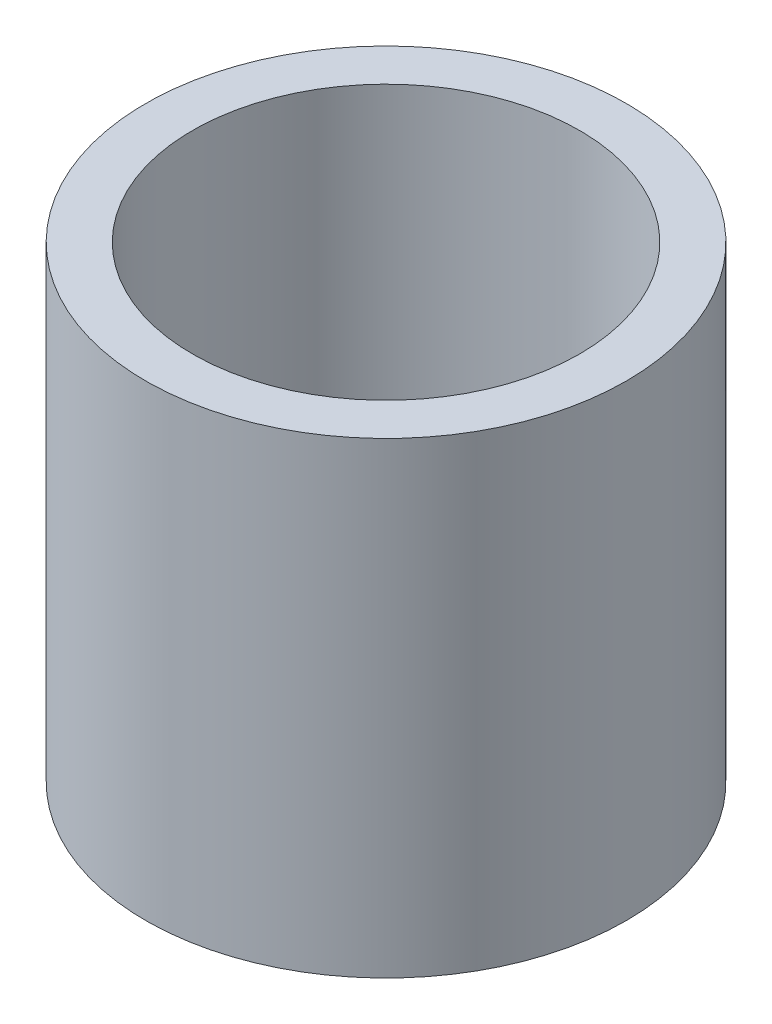
SolidWorks part; units mm, degrees
material "AISI 321 Annealed Stainless Steel (SS)"
ref_plane "Front Plane" through (0, 0, 0) normal (0, 0, 1) x (1, 0, 0)
ref_plane "Top Plane" through (0, 0, 0) normal (0, 1, 0) x (1, 0, 0)
ref_plane "Right Plane" through (0, 0, 0) normal (1, 0, 0) x (0, 0, -1)
sketch "Sketch1" plane through (0, 0, 0) normal (0, 0, 1) x (1, 0, 0)
  line L0 (0, -1459.8926) -> (0, 71534.7381) construction
  line L1 (16, -17.5) -> (16, -4.5)
  line L2 (16, -4.5) -> (14.5, -4.5)
  line L5 (14.5, -4.5) -> (14.5, 17.5)
  line L6 (14.5, 17.5) -> (18, 17.5)
  line L7 (18, 17.5) -> (18, -17.5)
  line L8 (18, -17.5) -> (16, -17.5)
  point P7 (0, 0)
  point P12 (18, 0)
  dimension "D1" = 35
  dimension "D2" = 36
  dimension "D3" = 32
  dimension "D4" = 22
  dimension "D5" = 29
revolve "Revolve1" add sketch "Sketch1" angle 360 about L0
